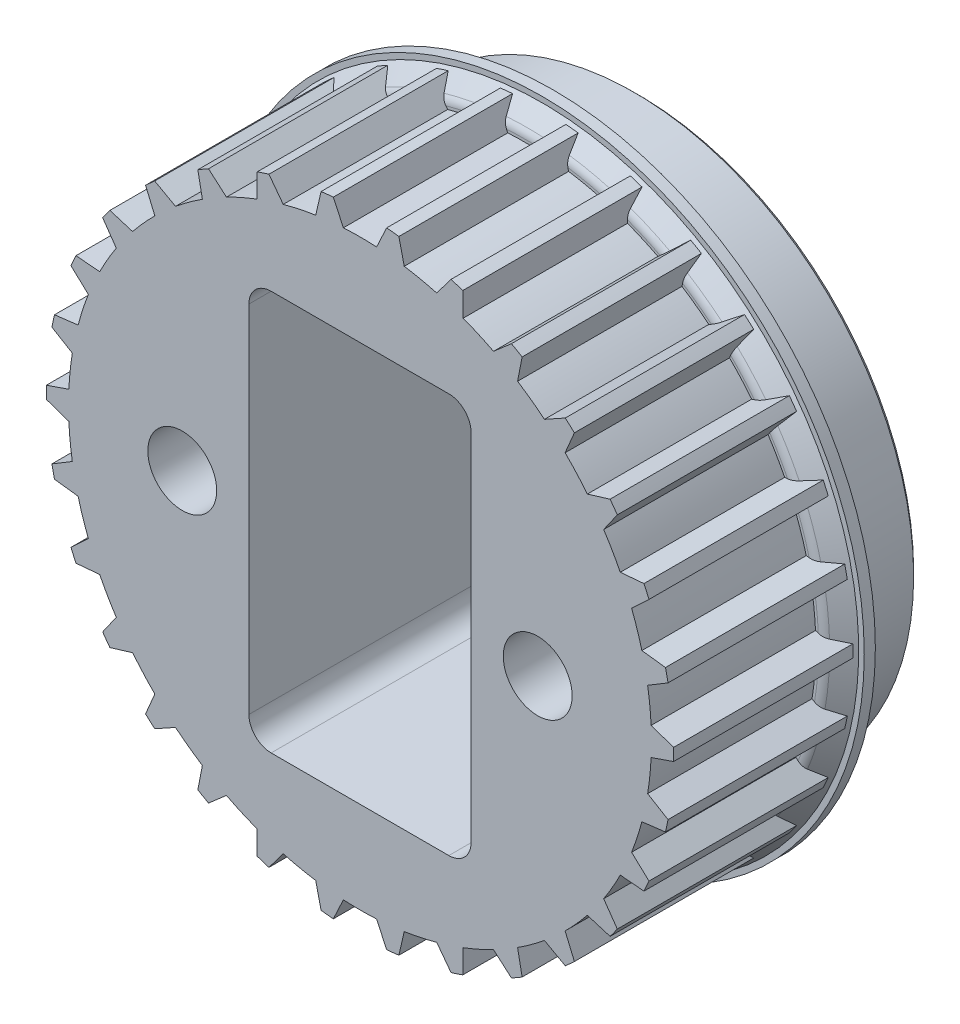
SolidWorks part; units mm, degrees
material "PMMA"
ref_plane "Ebene vorne" through (0, 0, 0) normal (0, 0, 1) x (1, 0, 0)
ref_plane "Ebene oben" through (0, 0, 0) normal (0, 1, 0) x (1, 0, 0)
ref_plane "Ebene rechts" through (0, 0, 0) normal (1, 0, 0) x (0, 0, -1)
ref_axis "Achse1" through (0, 0, 9.02) along (0, 0, -1)
sketch "Skizze1" plane through (0, 0, 0) normal (1, 0, 0) x (0, 0, -1)
  line L0 (0, 47.6717) -> (0, -53.1541) construction
  line L1 (-46.5152, 0) -> (56.3665, 0) construction
  line L2 (-4.35, 14.12) -> (4.35, 14.12)
  line L3 (4.35, 14.12) -> (4.35, 12.575)
  line L4 (4.35, 12.575) -> (8.2, 12.575)
  line L5 (8.2, 12.575) -> (8.2, 0)
  line L9 (-4.35, 14.12) -> (-4.35, 12.575)
  line L10 (-4.35, 12.575) -> (-4.35, 0)
  line L11 (-4.35, 0) -> (8.2, 0)
  point P12 (0, 0)
  point P15 (0, 14.12)
  dimension "D3" = 28.24
  dimension "D4" = 8.7
revolve "Rotation1" add sketch "Skizze1" angle 360 about L1
sketch "Skizze2" plane through (0, 0, 0) normal (0, 0, 1) x (1, 0, 0)
  line L0 (0, 30.4501) -> (0, -26.4561) construction
  line L1 (-21.1101, 0) -> (22.7837, 0) construction
  line L2 (-1.2, 14.0689) -> (-0.7476, 13.0987)
  line L3 (1.2, 14.0689) -> (0.7476, 13.0987)
  circle A0 centre (0, 0) radius 13.12 construction
  circle A1 centre (0, 0) radius 14.12 construction
  circle A2 centre (0, 0) radius 14.12 construction
  arc A3 (-1.2, 14.0689) -> (1.2, 14.0689) centre (0, 0) cw
  arc A4 (-0.7476, 13.0987) -> (0.7476, 13.0987) centre (0, 0) cw
  dimension "D1" = 28.24
  dimension "D2" = 26.24
  dimension "D6" = 1
  dimension "D3" = 50
  dimension "D4" = 2.4
  dimension "D5" = 1.4951
extrude "Schnitt-Linear austragen1" cut sketch "Skizze2" against normal through all and the other way through all
pattern_circular "Kreismuster1" count 30 over 360 about axis through (0, 0, 9.02) along (0, 0, -1) of "Schnitt-Linear austragen1"
sketch "Skizze3" plane through (0, 0, 0) normal (1, 0, 0) x (0, 0, -1)
  line L0 (4.35, 13) -> (4.35, 14.5)
  line L1 (4.35, 14.5) -> (3.85, 14.5)
  line L2 (3.85, 14.5) -> (3.85, 14.25)
  line L3 (3.85, 14.25) -> (3.1964, 13.5964)
  line L4 (3.05, 13.2429) -> (3.05, 13)
  line L5 (3.05, 13) -> (4.35, 13)
  line L6 (4.35, 13.0987) -> (4.35, 14.0689) construction
  line L7 (0, 19.3181) -> (0, -13.1661) construction
  line L8 (11.0313, 0) -> (-11.7934, 0) construction
  arc A0 (3.05, 13.2429) -> (3.1964, 13.5964) centre (3.55, 13.2429) cw
  dimension "D7" = 0.5
  dimension "D1" = 14.5
  dimension "D2" = 13
  dimension "D3" = 0.5
  dimension "D4" = 14.25
  dimension "D5" = 45
  dimension "D6" = 0.8
revolve "Rotation2" add sketch "Skizze3" angle 360 about L8
sketch "Skizze4" plane through (0, 0, 0) normal (0, 0, 1) x (1, 0, 0)
  line L0 (0, 24.4145) -> (0, -17.917) construction
  line L1 (-17.7015, 0) -> (18.3014, 0) construction
  line L2 (4, 9) -> (-4, 9)
  line L3 (-5, 8) -> (-5, -8)
  line L4 (5, 8) -> (5, -8)
  line L5 (4, -9) -> (-4, -9)
  arc A0 (-5, 8) -> (-4, 9) centre (-4, 8) cw
  arc A1 (5, 8) -> (4, 9) centre (4, 8) ccw
  arc A2 (5, -8) -> (4, -9) centre (4, -8) cw
  arc A3 (-5, -8) -> (-4, -9) centre (-4, -8) ccw
  circle A4 centre (-8, 0) radius 1.55
  circle A5 centre (8, 0) radius 1.55
  point P13 (-5, 0)
  point P14 (0, 9)
  point P20 (0, -9)
  point P21 (5, 0)
  dimension "D1" = 1
  dimension "D4" = 3.1
  dimension "D2" = 18
  dimension "D3" = 10
  dimension "D5" = 16
extrude "Schnitt-Linear austragen2" cut sketch "Skizze4" against normal through all and the other way through all
fillet "Verrundung1" radius 1.2 8 edges at (-4.7071, 8.7071, -8.2) (0, 9, -8.2) (4.7071, 8.7071, -8.2) (5, 0, -8.2) (4.7071, -8.7071, -8.2) (0, -9, -8.2) (-4.7071, -8.7071, -8.2) (-5, 0, -8.2)
chamfer "Fase1" distance 0.2 angle 45 3 edges at (-6.45, 0, -8.2) (6.45, 0, -8.2) (12.575, 0, -8.2)
